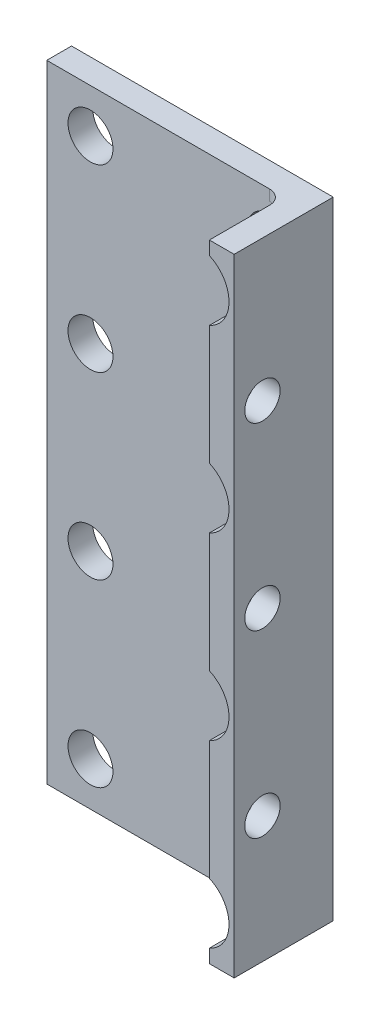
SolidWorks part; units mm, degrees
material "ABS"
ref_plane "Front Plane" through (0, 0, 0) normal (0, 0, 1) x (1, 0, 0)
ref_plane "Top Plane" through (0, 0, 0) normal (0, 1, 0) x (1, 0, 0)
ref_plane "Right Plane" through (0, 0, 0) normal (1, 0, 0) x (0, 0, -1)
sketch "Sketch1" plane through (0, 0, 0) normal (0, 0, 1) x (1, 0, 0)
  line L0 (6.175, 3) -> (6.175, 0) construction
  line L1 (0, 0) -> (33.475, 0)
  line L2 (0, 0) -> (0, 88.55)
  line L3 (0, 88.55) -> (33.475, 88.55)
  line L4 (33.475, 0) -> (33.475, 88.55)
  line L5 (3, 6.175) -> (0, 6.175) construction
  line L6 (33.475, 0) -> (36.975, 0)
  line L7 (36.975, 0) -> (36.975, 88.55)
  line L8 (36.975, 88.55) -> (33.475, 88.55)
  line L9 (3, 82.375) -> (0, 82.375) construction
  line L10 (6.175, 85.55) -> (6.175, 88.55) construction
  line L11 (6.175, 82.375) -> (31.575, 82.375) construction
  line L12 (31.575, 82.375) -> (36.975, 82.375) construction
  circle A0 centre (6.175, 6.175) radius 3.175
  circle A1 centre (6.175, 82.375) radius 3.175
  circle A2 centre (31.575, 82.375) radius 3.175
  circle A3 centre (31.575, 6.175) radius 3.175
  circle A4 centre (31.575, 31.575) radius 3.175
  circle A5 centre (31.575, 56.975) radius 3.175
  circle A6 centre (6.175, 31.575) radius 3.175
  circle A7 centre (6.175, 56.975) radius 3.175
  circle A8 centre (31.575, 6.175) radius 4.675
  circle A9 centre (31.575, 31.575) radius 4.675
  circle A10 centre (31.575, 56.975) radius 4.675
  circle A11 centre (31.575, 82.375) radius 4.675
  dimension "D2" = 6.35
  dimension "D9" = 1.5
  dimension "D1" = 3
  dimension "D3" = 76.2
  dimension "D4" = 25.4
  dimension "D5" = 5.4
  dimension "D6" = 3.5
  dimension "D7" = 2
  dimension "D8" = 3
extrude "Boss-Extrude1" add sketch "Sketch1" against normal blind 3.5 contours A5 L4 A2 L3 L2 L1 A3 A4 A7 A6 A1 A0 | A5 L4 A4 A3 L6 L7 L8 A2 | L4 A11 A2 | L4 A11 A2 | L4 A10 A5 | L4 A10 A5 | L4 A9 A4 | L4 A9 A4 | L4 A8 A3 | L4 A8 A3 region at (16.1613, 44.275, 0) region at (35.3962, 44.275, 0) region at (27.0143, 6.175, 0) region at (34.8451, 6.175, 0) region at (34.8451, 82.375, 0) region at (33.3607, 85.7826, 0) region at (27.0143, 31.575, 0) region at (34.8451, 31.575, 0) region at (34.8451, 56.975, 0) region at (33.3607, 60.3826, 0)
extrude "Boss-Extrude3" add sketch "Sketch1<4>" along normal offset from surface (10.5 mm away) 14 contours A11 L4 A10 A9 A8 L6 L7 L8 | L4 A11 A2 | L4 A10 A5 | L4 A9 A4 | L4 A8 A3 region at (35.3962, 44.275, 0) region at (34.8451, 6.175, 0) region at (34.8451, 82.375, 0) region at (34.8451, 31.575, 0) region at (34.8451, 56.975, 0) up to face at (34.75, 82.375, -3.5)
sketch "Sketch1<4>" plane through (0, 0, 0) normal (0, 0, 1) x (1, 0, 0) same geometry as "Sketch1"
extrude "Cut-Extrude1" cut sketch "Sketch1<5>" along normal up to surface (10.5 mm away) contours L4 A11 A2 | L4 A10 A5 | L4 A9 A4 | L4 A8 A3 region at (34.8451, 6.175, 0) region at (34.8451, 82.375, 0) region at (34.8451, 31.575, 0) region at (34.8451, 56.975, 0) up to face at (34.4834, 44.275, 10.5)
sketch "Sketch1<5>" plane through (0, 0, 0) normal (0, 0, 1) x (1, 0, 0) same geometry as "Sketch1"
sketch "Sketch2" plane through (36.975, 0, 0) normal (1, 0, 0) x (0, 0, -1)
  line L0 (3.5, 0) -> (-10.5, 0) construction
  line L1 (3.5, 88.55) -> (-10.5, 88.55) construction
  line L2 (-6.5, 0) -> (-6.5, 88.55) construction
  line L3 (3.5, 0) -> (-10.5, 0) construction
  line L4 (3.5, 0) -> (3.5, 88.55) construction
  circle A0 centre (-6.5, 17.8493) radius 2.5
  circle A1 centre (-6.5, 43.2493) radius 2.5
  circle A2 centre (-6.5, 68.6493) radius 2.5
  dimension "D3" = 5
  dimension "D1" = 17.8493
  dimension "D2" = 10
  dimension "D4" = 3
extrude "Cut-Extrude2" cut sketch "Sketch2" against normal up to surface (3.5 mm away) up to face at (33.475, 16.7679, 5.25)
fillet "Fillet1" radius 2 5 edges
